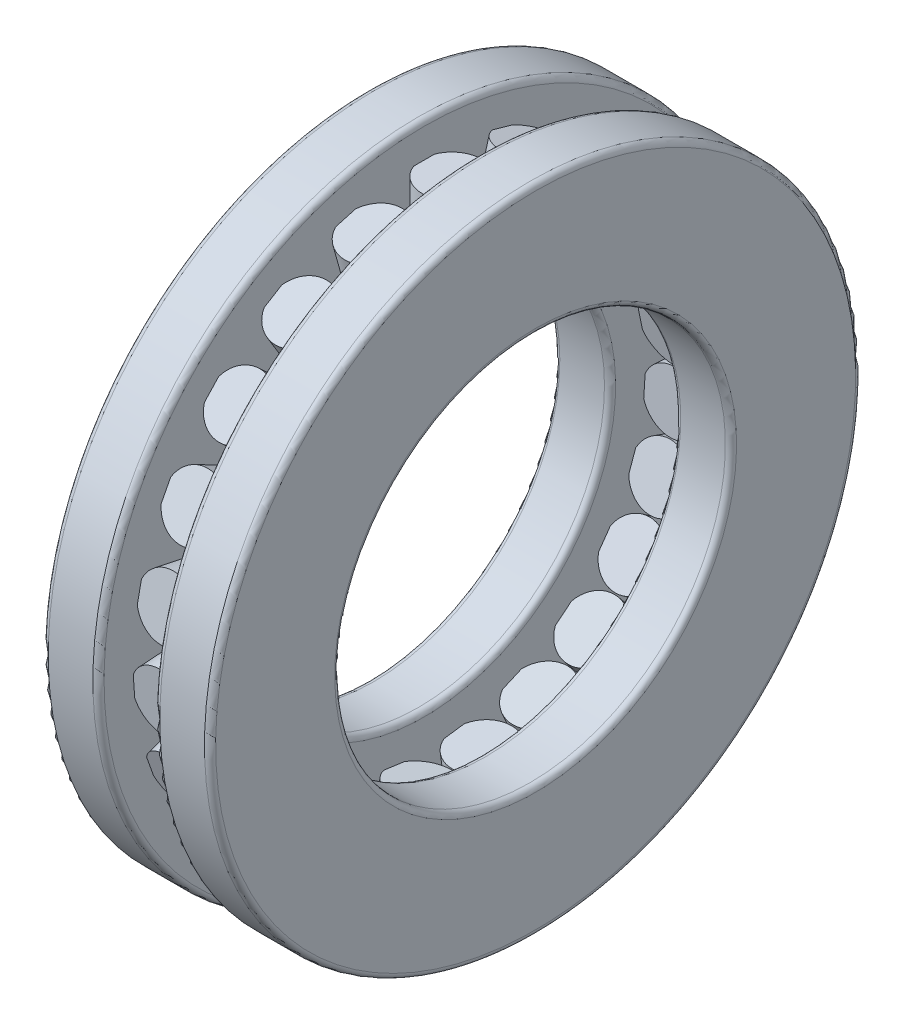
SolidWorks part; units mm, degrees
ref_plane "Front" through (0, 0, 0) normal (0, 0, 1) x (1, 0, 0)
ref_plane "Top" through (0, 0, 0) normal (0, 1, 0) x (1, 0, 0)
ref_plane "Right" through (0, 0, 0) normal (1, 0, 0) x (0, 0, -1)
sketch "Sketch1" plane through (-7.03, 10.47, 0) normal (0, 0, 1) x (0, 1, 0)
  line L0 (-10.47, 18.1553) -> (-10.47, -14.7153) construction
  line L1 (-27.97, 1.97) -> (-20.47, 1.97) construction
  line L2 (-27.97, -7.03) -> (-20.47, -7.03)
  line L3 (-27.97, -7.03) -> (-27.97, -4.03)
  line L4 (-27.97, -4.03) -> (-20.47, -4.03)
  line L5 (-20.47, -7.03) -> (-20.47, -4.03)
  dimension "D3" = 3
revolve "Revolve1" add sketch "Sketch1" angle 360 about L0
sketch "Sketch2" plane through (1.5709, -3.0291, 0) normal (0, 0, 1) x (0, -1, 0)
  line L0 (-19.5753, -0.0709) -> (17.0395, -0.0709) construction
  line L2 (-18.6541, -0.0709) -> (-18.6541, 1.5291)
  line L4 (-18.6541, 1.5291) -> (-14.9041, 1.5291)
  line L5 (-14.9041, 1.5291) -> (-14.9041, -0.0709)
  line L7 (-18.6541, -0.0709) -> (-14.9041, -0.0709)
  dimension "D4" = 1.5
  dimension "D3" = 3.75
  dimension "D2" = 11.875
  dimension "D1" = 3.2
revolve "Revolve2" add sketch "Sketch2" angle 360 about L0
sketch "Sketch3" plane through (-8.783, 8.717, 0) normal (0, 0, 1) x (0, 1, 0)
  line L0 (-8.717, 6.8297) -> (-8.717, -6.8957) construction
  line L1 (-26.217, -11.783) -> (-19.217, -11.783)
  line L2 (-26.217, -11.783) -> (-26.217, -14.783)
  line L3 (-26.217, -14.783) -> (-19.217, -14.783)
  line L4 (-19.217, -11.783) -> (-19.217, -14.783)
  line L5 (3.158, -11.883) -> (6.908, -11.883) construction
  dimension "D2" = 3
  dimension "D1" = 0.1
revolve "Revolve3" add sketch "Sketch3" angle 360 about L0
pattern_circular "Circular-Pattern1" count 23 over 360 about axis through (-25.1853, 0, 0) along (1, 0, 0) of "Revolve2"
fillet "Fillet1" radius 0.3 8 edges at (0, -17.5, 0) (-3, -17.5, 0) (-3, -10, 0) (0, -10, 0) (3, -10.5, 0) (6, -10.5, 0) (6, -17.5, 0) (3, -17.5, 0)
equation "\"D3@Sketch1\" = \"H@Sketch1\" / 3"
equation "\"D1@Sketch2\" = \"H@Sketch1\" / 3 + 0.2"
equation "\"D4@Sketch2\" = \"D1@Sketch2\" / 2 - 0.1"
equation "\"D3@Sketch2\" =  ( \"DD1@Sketch1\" - \"XD@Sketch1\" )  / 4"
equation "\"D2@Sketch2\" = \"XD@Sketch1\" / 2 +  ( \"DD1@Sketch1\" - \"XD@Sketch1\" )  / 8"
equation "\"D1@Circular-Pattern1\" = int ( 3.14 / atn (  ( \"D1@Sketch2\" / 2 )  / sqr (  ( \"D2@Sketch2\" * \"D2@Sketch2\" )  -  ( \"D1@Sketch2\" / 2 )  *  ( \"D1@Sketch2\" / 2 )  )  )  )"
equation "\"D2@Sketch3\" = \"H@Sketch1\" / 3"
